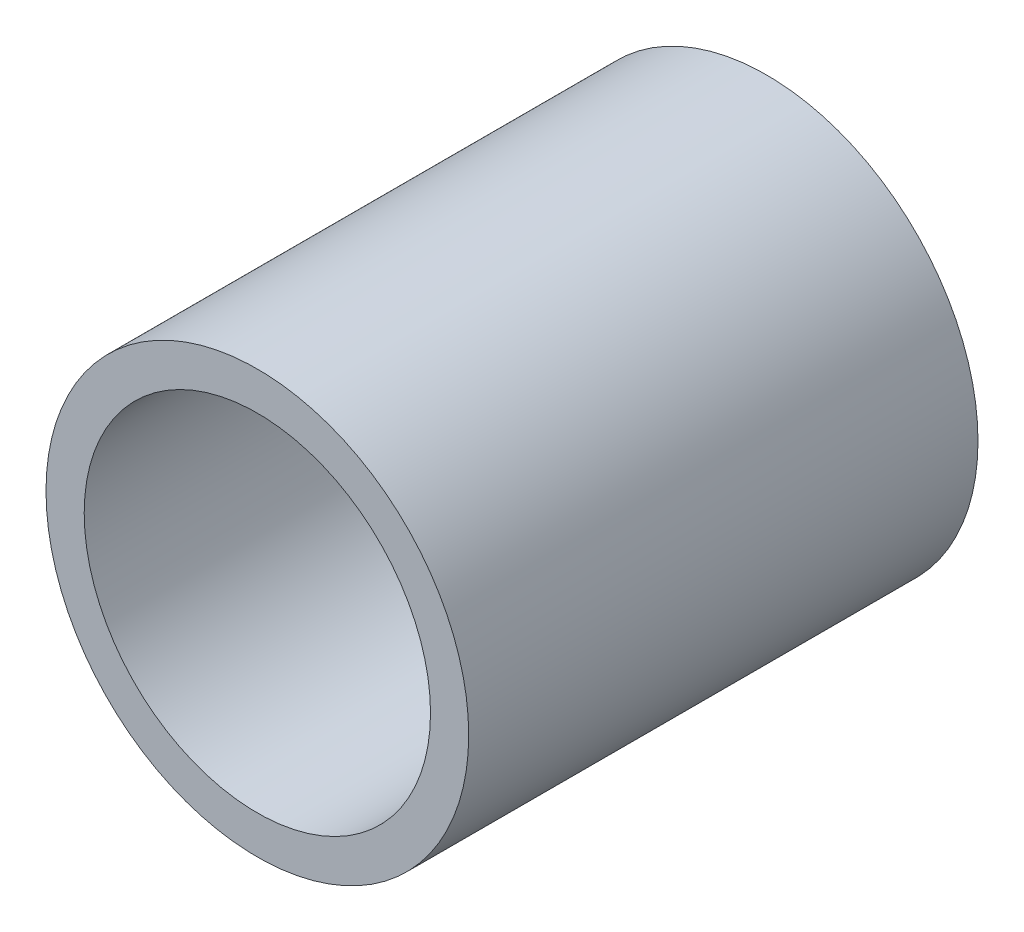
SolidWorks part; units mm, degrees
ref_plane "Front Plane" through (0, 0, 0) normal (0, 0, 1) x (1, 0, 0)
ref_plane "Top Plane" through (0, 0, 0) normal (0, 1, 0) x (1, 0, 0)
ref_plane "Right Plane" through (0, 0, 0) normal (1, 0, 0) x (0, 0, -1)
sketch "Sketch2" plane through (0, 0, 0) normal (0, 0, 1) x (1, 0, 0)
  circle A0 centre (0, 0) radius 17.272
  circle A1 centre (0, 0) radius 21.082
  dimension "D1" = 34.544
  dimension "D2" = 42.164
extrude "Boss-Extrude1" add sketch "Sketch2" along normal blind 50.8 contours A1 A0 region at (-20.4857, 0, 0)
